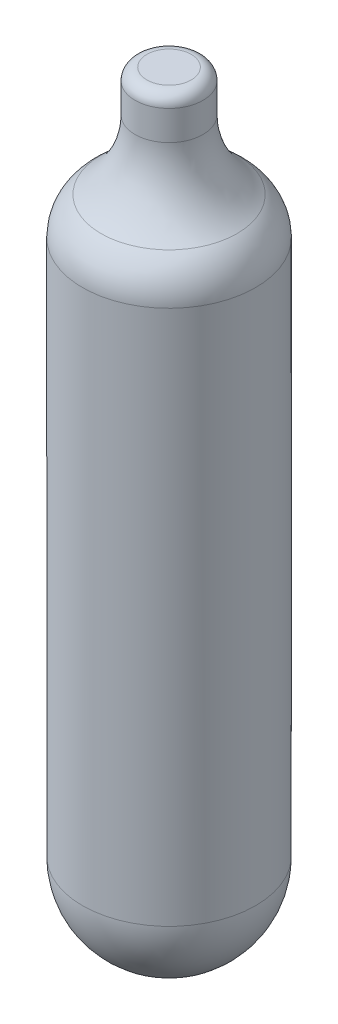
SolidWorks part; units mm, degrees
ref_plane "Front Plane" through (0, 0, 0) normal (0, 0, 1) x (1, 0, 0)
ref_plane "Top Plane" through (0, 0, 0) normal (0, 1, 0) x (1, 0, 0)
ref_plane "Right Plane" through (0, 0, 0) normal (1, 0, 0) x (0, 0, -1)
sketch "Sketch2" plane through (0, 0, 0) normal (0, 1, 0) x (1, 0, 0)
  circle A0 centre (0, 0) radius 9.3218
extrude "Boss-Extrude1" add sketch "Sketch2" along normal blind 82.8802
fillet "Fillet1" radius 9.3218 1 edges at (0, 0, 9.3218)
sketch "Sketch3" plane through (0, 82.8802, 0) normal (0, 1, 0) x (1, 0, 0)
  circle A0 centre (0, 0) radius 3.6576
  circle A1 centre (0, 0) radius 9.3218
extrude "Cut-Extrude1" cut sketch "Sketch3" against normal blind 13.0302
fillet "Fillet2" radius 9.3218 1 edges at (0, 69.85, 3.6576)
fillet "Fillet3" radius 5.08 1 edges at (0, 69.85, 9.3218)
fillet "Fillet5" radius 1.27 1 edges at (0, 82.8802, 3.6576)
